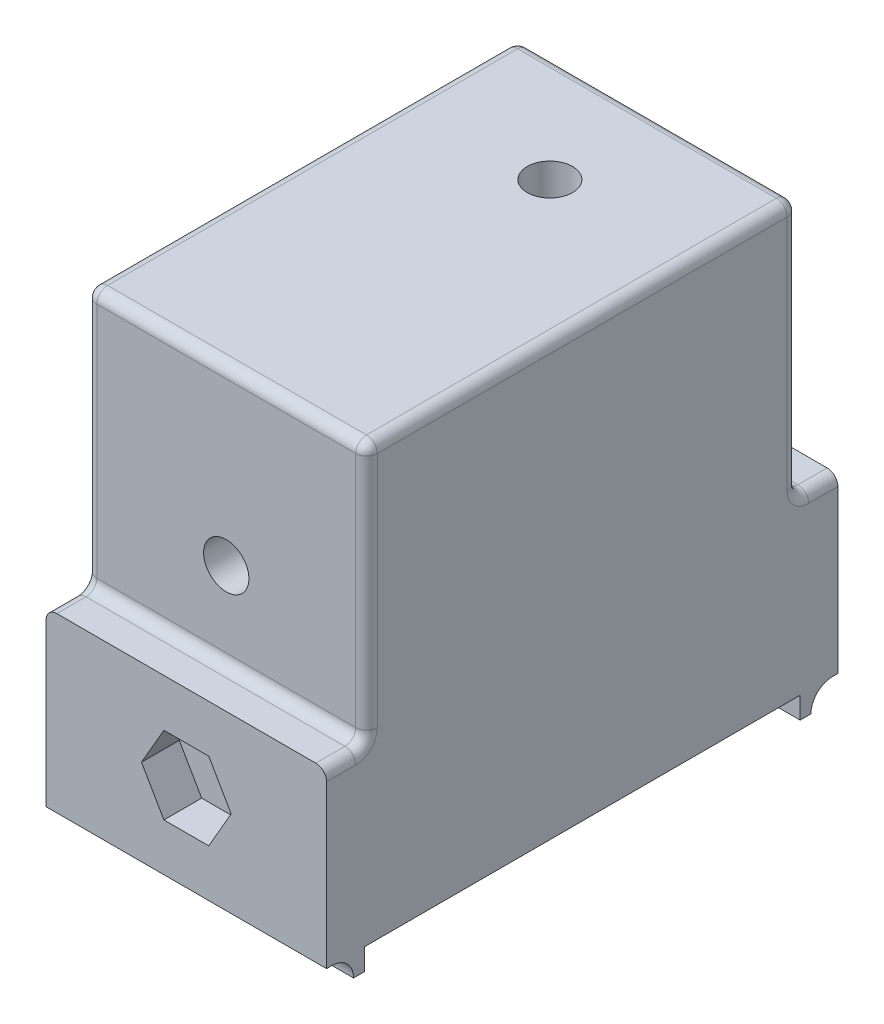
SolidWorks part; units mm, degrees
ref_plane "Front Plane" through (0, 0, 0) normal (0, 0, 1) x (1, 0, 0)
ref_plane "Top Plane" through (0, 0, 0) normal (0, 1, 0) x (1, 0, 0)
ref_plane "Right Plane" through (0, 0, 0) normal (1, 0, 0) x (0, 0, -1)
sketch "Sketch1" plane through (0, 0, 0) normal (0, 1, 0) x (1, 0, 0)
  line L1 (-13, 20) -> (13, 20)
  line L2 (-13, 20) -> (-13, -20)
  line L3 (-13, -20) -> (13, -20)
  line L4 (13, 20) -> (13, -20)
  line L5 (-13, 20) -> (13, -20) construction
  line L6 (-13, -20) -> (13, 20) construction
  point P4 (0, 0)
  dimension "D1" = 40
  dimension "D2" = 26
extrude "Boss-Extrude1" add sketch "Sketch1" along normal blind 40
sketch "Sketch2" plane through (0, 0, 0) normal (0, -1, 0) x (1, 0, 0)
  line L1 (-13, 23.7) -> (13, 23.7)
  line L2 (-13, 23.7) -> (-13, 20)
  line L3 (-13, 20) -> (13, 20)
  line L4 (13, 23.7) -> (13, 20)
  line L5 (-13, 23.7) -> (13, 20) construction
  line L6 (-13, 20) -> (13, 23.7) construction
  line L7 (-13, -20) -> (13, -20)
  line L8 (-13, -20) -> (-13, -23.7)
  line L9 (-13, -23.7) -> (13, -23.7)
  line L10 (13, -20) -> (13, -23.7)
  line L11 (-13, -20) -> (13, -23.7) construction
  line L12 (-13, -23.7) -> (13, -20) construction
  point P4 (0, 21.85)
  point P12 (0, -21.85)
  dimension "D1" = 3.7
  dimension "D2" = 3.7
extrude "Boss-Extrude2" add sketch "Sketch2" against normal blind 16
sketch "Sketch3" plane through (0, 0, -23.7) normal (0, 0, -1) x (-1, 0, 0)
  line L0 (-13, 16) -> (13, 0) construction
  line L1 (13, 16) -> (-13, 0) construction
  line L3 (2.0785, 11.6) -> (-2.0785, 11.6)
  line L4 (-2.0785, 11.6) -> (-4.1569, 8)
  line L5 (-4.1569, 8) -> (-2.0785, 4.4)
  line L6 (-2.0785, 4.4) -> (2.0785, 4.4)
  line L7 (2.0785, 4.4) -> (4.1569, 8)
  line L8 (4.1569, 8) -> (2.0785, 11.6)
  circle A1 centre (0, 8) radius 3.6 construction
  dimension "D1" = 7.2
sketch "Sketch5" plane through (0, 0, 0) normal (0, -1, 0) x (1, 0, 0)
  line L0 (-13, -23.7) -> (-13, 23.7) construction
  line L1 (-10, 17) -> (10, 17)
  line L2 (-10, 17) -> (-10, -17)
  line L3 (-10, -17) -> (10, -17)
  line L4 (10, 17) -> (10, -17)
  line L5 (-10, 17) -> (10, -17) construction
  line L6 (-10, -17) -> (10, 17) construction
  line L8 (13, -20) -> (-13, -20) construction
  line L9 (13, -20) -> (-13, -20) construction
  point P4 (0, 0)
  dimension "D1" = 3
  dimension "D2" = 3
extrude "Cut-Extrude3" cut sketch "Sketch5" against normal blind 37
fillet "Fillet1" radius 1 14 edges at (0, 16, 20) (0, 16, -20) (13, 16, 21.85) (13, 28, 20) (13, 28, -20) (13, 16, -21.85) (-13, 16, -21.85) (-13, 28, -20) (-13, 28, 20) (-13, 16, 21.85) (0, 40, -20) (13, 40, 0) (0, 40, 20) (-13, 40, 0)
fillet "Fillet2" radius 1 8 edges at (0, 37, 17) (10, 37, 0) (0, 37, -17) (-10, 37, 0) (-10, 18.5, -17) (10, 18.5, -17) (-10, 18.5, 17) (10, 18.5, 17)
sketch "Sketch8" plane through (0, 0, 0) normal (0, -1, 0) x (1, 0, 0)
  line L0 (-13, 20) -> (13, 20) construction
  line L1 (-13, 20) -> (13, 20) construction
  line L2 (0, 0) -> (0, 20) construction
  line L8 (-13, -23.7) -> (13, -23.7)
  line L13 (13, -23.7) -> (13, 23.7)
  line L14 (13, 23.7) -> (-13, 23.7)
  line L15 (-13, 23.7) -> (-13, -23.7)
  line L16 (-13, -23.7) -> (13, -23.7)
  line L21 (13, -23.7) -> (13, 23.7)
  line L22 (13, 23.7) -> (-13, 23.7)
  line L23 (-13, 23.7) -> (-13, -23.7)
  circle A0 centre (0, 0) radius 20 construction
  dimension "D2" = 20
  dimension "D1" = 0
extrude "Cut-Extrude6" cut sketch "Sketch3" against normal blind 3.5
sketch "Measure Shearing Area" plane through (0, 0, -23.7) normal (0, 0, -1) x (-1, 0, 0)
  line L0 (-4.1569, 8) -> (-4.1569, 0)
  line L1 (13, 0) -> (-13, 0) construction
  line L2 (-4.1569, 0) -> (4.1569, 0)
  line L3 (4.1569, 0) -> (4.1569, 8)
  line L4 (4.1569, 8) -> (2.0785, 4.4)
  line L5 (2.0785, 4.4) -> (-2.0785, 4.4)
  line L6 (-2.0785, 4.4) -> (-4.1569, 8)
mirror "Mirror2" about plane through (0, 0, 0) normal (0, 0, 1) of "Cut-Extrude6"
sketch "Sketch9" plane through (0, 0, 0) normal (0, -1, 0) x (1, 0, 0)
  line L0 (-13, -23.7) -> (-13, 23.7) construction
  line L1 (-13, 21.2) -> (13, 21.2)
  line L2 (-13, 21.2) -> (-13, 20.2)
  line L3 (-13, 20.2) -> (13, 20.2)
  line L4 (13, 21.2) -> (13, 20.2)
  line L5 (-13, 21.2) -> (13, 20.2) construction
  line L6 (-13, 20.2) -> (13, 21.2) construction
  line L7 (13, 23.7) -> (13, -23.7) construction
  line L8 (-13, 0) -> (13, 0) construction
  line L9 (-13, -20.2) -> (13, -20.2)
  line L10 (13, -21.2) -> (13, -20.2)
  line L11 (-13, -21.2) -> (13, -21.2)
  line L12 (-13, -21.2) -> (-13, -20.2)
  point P4 (0, 20.7)
  dimension "D1" = 20.2
  dimension "D2" = 1
extrude "Boss-Extrude3" add sketch "Sketch9" along normal blind 2
sketch "Sketch12" plane through (0, 0, 20) normal (0, 0, 1) x (1, 0, 0)
  line L0 (-13, 28) -> (13, 28) construction
  line L1 (0, 0) -> (0, 40) construction
  line L2 (-12, 40) -> (12, 40) construction
  line L3 (-13, 17) -> (-13, 39) construction
  line L4 (13, 39) -> (13, 17) construction
  line L6 (-12, 21.9) -> (12, 21.9) construction
  line L7 (-12, 39) -> (-12, 17) construction
  line L8 (12, 17) -> (12, 39) construction
  line L9 (12, 16) -> (-12, 16) construction
  circle A1 centre (0, 24) radius 2.1
  dimension "D1" = 4.2
  dimension "D2" = 4
  dimension "D3" = 5.9
sketch "Sketch13" plane through (0, 40, 0) normal (0, 1, 0) x (1, 0, 0)
  line L0 (-13, 0) -> (13, 0) construction
  line L1 (0, 23.7) -> (0, -23.7) construction
  line L2 (13, 19) -> (13, -19) construction
  line L3 (-13, -19) -> (-13, 19) construction
  line L4 (-12, 23.7) -> (12, 23.7) construction
  line L5 (12, -23.7) -> (-12, -23.7) construction
  circle A1 centre (0, 10) radius 2.1
  dimension "D1" = 4.2
  dimension "D2" = 10
extrude "Cut-Extrude7" cut sketch "Sketch12" against normal up to next
extrude "Cut-Extrude8" cut sketch "Sketch13" against normal up to next
fillet "Fillet3" radius 2 2 edges at (0, 0, 21.2) (0, 0, -21.2)
